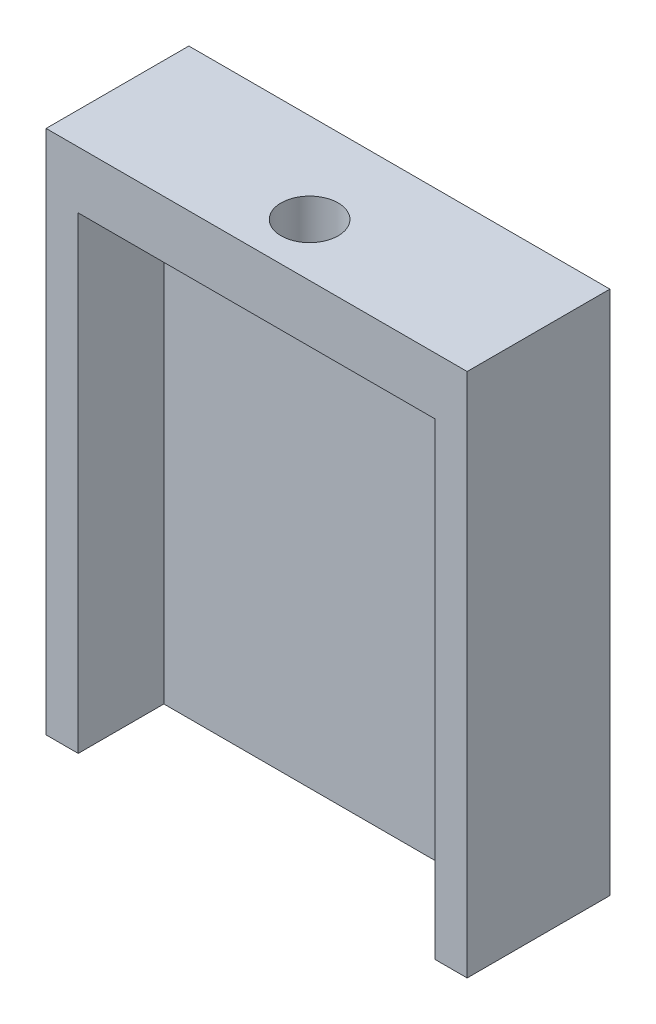
SolidWorks part; units mm, degrees
ref_plane "Front Plane" through (0, 0, 0) normal (0, 0, 1) x (1, 0, 0)
ref_plane "Top Plane" through (0, 0, 0) normal (0, 1, 0) x (1, 0, 0)
ref_plane "Right Plane" through (0, 0, 0) normal (1, 0, 0) x (0, 0, -1)
sketch "Sketch1" plane through (0, 0, 0) normal (0, 1, 0) x (1, 0, 0)
  line L0 (-7.375, -1) -> (-7.375, -4.0005)
  line L1 (-7.375, 1) -> (7.375, 1)
  line L2 (-7.375, 1) -> (-7.375, -1)
  line L4 (7.375, 1) -> (7.375, -1)
  line L5 (-7.375, 1) -> (7.375, -1) construction
  line L6 (-7.375, -1) -> (7.375, 1) construction
  line L7 (-7.375, -4.0005) -> (-6.25, -4.0005)
  line L8 (-6.25, -4.0005) -> (-6.25, -1)
  line L9 (-6.25, -1) -> (6.25, -1)
  line L10 (6.25, -1) -> (6.25, -4.0005)
  line L11 (6.25, -4.0005) -> (7.375, -4.0005)
  line L12 (7.375, -4.0005) -> (7.375, -1)
  point P1 (0, 0)
  dimension "D1" = 14.75
  dimension "D2" = 2
  dimension "D3" = 12.5
  dimension "D4" = 1.125
extrude "Boss-Extrude1" add sketch "Sketch1" along normal blind 16.4
sketch "Sketch2" plane through (0, 16.4, 0) normal (0, 1, 0) x (1, 0, 0)
  line L0 (-6.25, -4.0005) -> (6.25, -4.0005)
  line L8 (7.375, -4.0005) -> (7.375, 1)
  line L9 (7.375, 1) -> (-7.375, 1)
  line L10 (-7.375, 1) -> (-7.375, -4.0005)
  line L11 (-7.375, -4.0005) -> (-6.25, -4.0005)
  line L12 (-6.25, -4.0005) -> (-6.25, -1)
  line L13 (-6.25, -1) -> (6.25, -1)
  line L14 (6.25, -1) -> (6.25, -4.0005)
  line L15 (6.25, -4.0005) -> (7.375, -4.0005)
  line L16 (7.375, -4.0005) -> (7.375, 1)
  line L17 (7.375, 1) -> (-7.375, 1)
  line L18 (-7.375, 1) -> (-7.375, -4.0005)
  line L19 (-7.375, -4.0005) -> (-6.25, -4.0005)
  line L23 (6.25, -4.0005) -> (7.375, -4.0005)
  dimension "D1" = 0
extrude "Boss-Extrude2" add sketch "Sketch2" along normal blind 2
sketch "Sketch3" plane through (0, 18.4, 0) normal (0, 1, 0) x (1, 0, 0)
  line L0 (-7.375, -2.1449) -> (7.375, -2.1449) construction
  line L1 (-7.375, 1) -> (-7.375, -4.0005) construction
  line L2 (7.375, -4.0005) -> (7.375, 1) construction
  line L3 (0, 1) -> (0, -4.0005) construction
  line L4 (7.375, 1) -> (-7.375, 1) construction
  line L5 (-7.375, -4.0005) -> (7.375, -4.0005) construction
  circle A0 centre (0, -2.1449) radius 1
  point P14 (0, -2.2099)
  point P15 (0, -1.8932)
  point P16 (0, -2.058)
  point P17 (0, -2.1016)
  point P18 (0, -2.1449)
extrude "Cut-Extrude1" cut sketch "Sketch3" against normal through all
